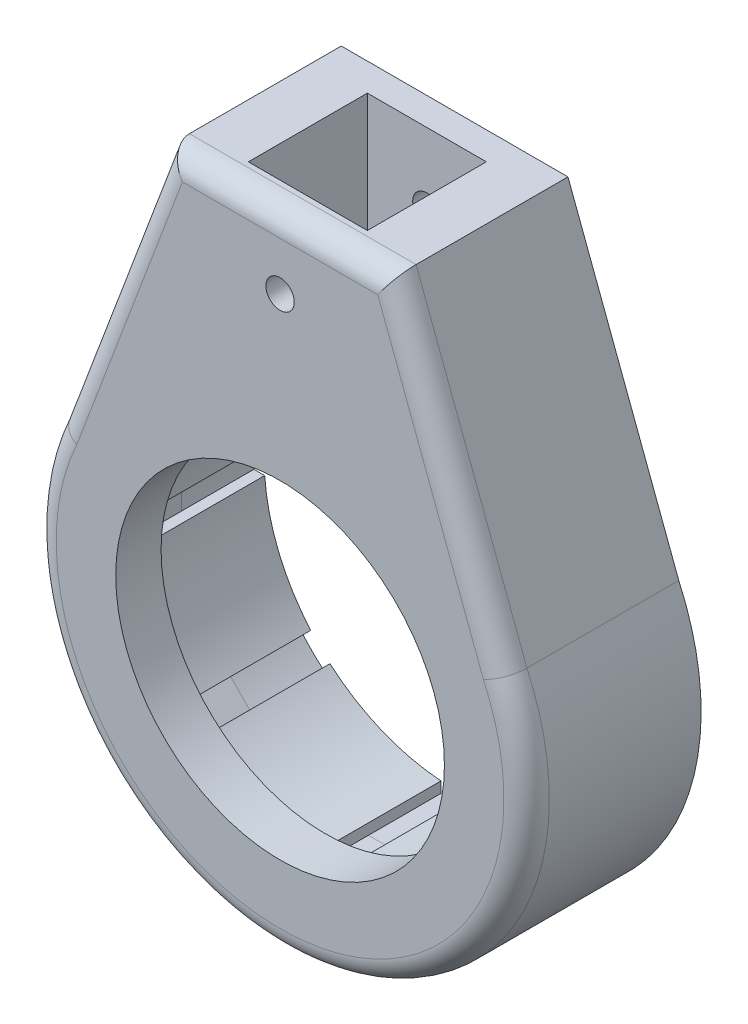
SolidWorks part; units mm, degrees
ref_plane "Alzado" through (0, 0, 0) normal (0, 0, 1) x (1, 0, 0)
ref_plane "Planta" through (0, 0, 0) normal (0, 1, 0) x (1, 0, 0)
ref_plane "Vista lateral" through (0, 0, 0) normal (1, 0, 0) x (0, 0, -1)
sketch "Croquis1" plane through (0, 0, 0) normal (0, 0, 1) x (1, 0, 0)
  line L0 (-43.5, 0) -> (43.5, 0) construction
  line L1 (0, 43.5) -> (0, -43.5) construction
  line L2 (0, 0) -> (-30.7591, 30.7591) construction
  line L3 (0, 0) -> (26.6453, -26.6453) construction
  line L4 (30.7591, 30.7591) -> (0, 0) construction
  line L5 (0, 0) -> (-30.7591, -30.7591) construction
  line L6 (-2.4, 33.5142) -> (-2.4, 35.4188)
  line L7 (2.4, 33.5142) -> (2.4, 35.4188)
  line L8 (2.4, -33.5142) -> (2.4, -35.4188)
  line L9 (-2.4, -33.5142) -> (-2.4, -35.4188)
  line L10 (-35.4188, 2.4) -> (-33.5142, 2.4)
  line L11 (-35.4188, -2.4) -> (-33.5142, -2.4)
  line L12 (35.4188, -2.4) -> (33.5142, -2.4)
  line L13 (35.4188, 2.4) -> (33.5142, 2.4)
  line L14 (-23.3478, 26.7419) -> (-22.001, 25.3952)
  line L15 (-26.7419, 23.3478) -> (-25.3952, 22.001)
  line L16 (26.7419, -23.3478) -> (25.3952, -22.001)
  line L17 (23.3478, -26.7419) -> (22.001, -25.3952)
  line L18 (22.001, 25.3952) -> (23.3478, 26.7419)
  line L19 (25.3952, 22.001) -> (26.7419, 23.3478)
  line L20 (-22.001, -25.3952) -> (-23.3478, -26.7419)
  line L21 (-25.3952, -22.001) -> (-26.7419, -23.3478)
  circle A0 centre (0, 0) radius 43.5
  arc A1 (-23.3478, 26.7419) -> (-26.7419, 23.3478) centre (0, 0) ccw
  arc A2 (-2.4, 33.5142) -> (-22.001, 25.3952) centre (0, 0) ccw
  arc A3 (2.4, 35.4188) -> (-2.4, 35.4188) centre (0, 0) ccw
  arc A4 (-25.3952, 22.001) -> (-33.5142, 2.4) centre (0, 0) ccw
  arc A5 (22.001, 25.3952) -> (2.4, 33.5142) centre (0, 0) ccw
  arc A6 (26.7419, 23.3478) -> (23.3478, 26.7419) centre (0, 0) ccw
  arc A7 (33.5142, 2.4) -> (25.3952, 22.001) centre (0, 0) ccw
  arc A8 (35.4188, -2.4) -> (35.4188, 2.4) centre (0, 0) ccw
  arc A9 (25.3952, -22.001) -> (33.5142, -2.4) centre (0, 0) ccw
  arc A10 (23.3478, -26.7419) -> (26.7419, -23.3478) centre (0, 0) ccw
  arc A11 (2.4, -33.5142) -> (22.001, -25.3952) centre (0, 0) ccw
  arc A12 (-2.4, -35.4188) -> (2.4, -35.4188) centre (0, 0) ccw
  arc A13 (-22.001, -25.3952) -> (-2.4, -33.5142) centre (0, 0) ccw
  arc A14 (-26.7419, -23.3478) -> (-23.3478, -26.7419) centre (0, 0) ccw
  arc A15 (-33.5142, -2.4) -> (-25.3952, -22.001) centre (0, 0) ccw
  arc A16 (-35.4188, 2.4) -> (-35.4188, -2.4) centre (0, 0) ccw
  dimension "D1" = 87
  dimension "D2" = 71
  dimension "D6" = 67.2
  dimension "D3" = 45
  dimension "D4" = 45
  dimension "D5" = 45
  dimension "D7" = 2.4
  dimension "D8" = 2.4
  dimension "D9" = 2.4
  dimension "D10" = 2.4
  dimension "D11" = 2.4
  dimension "D12" = 2.4
  dimension "D13" = 2.4
  dimension "D14" = 2.4
extrude "Saliente-Extruir4" add sketch "Croquis1" along normal blind 12.8 contours A0 | L14 A2 L6 A3 L7 A5 L18 A6 L19 A7 L13 A8 L12 A9 L16 A10 L17 A11 L8 A12 L9 A13 L20 A14 L21 A15 L11 A16 L10 A4 L15 A1
sketch "Croquis2" plane through (0, 0, 12.8) normal (0, 0, 1) x (1, 0, 0)
  line L0 (0, 0) -> (0, 115.8162) construction
  circle A0 centre (0, 0) radius 43.5
  dimension "D1" = 87
extrude "Saliente-Extruir5" add sketch "Croquis2" along normal blind 18
sketch "Croquis3" plane through (0, 0, 0) normal (0, 0, 1) x (1, 0, 0)
  line L0 (-43.5, 0) -> (43.5, 0) construction
  line L1 (43.5, 0) -> (20, 70) construction
  line L2 (20, 70) -> (-20, 70) construction
  line L3 (-20, 70) -> (-43.5, 0) construction
  line L4 (0, 0) -> (0, 70) construction
  line L5 (-20, 70) -> (-39.5567, 18.0975)
  line L6 (20, 70) -> (39.5567, 18.0975)
  line L7 (-20, 70) -> (20, 70)
  circle A0 centre (0, 0) radius 43.5 construction
  circle A2 centre (0, 0) radius 43.5
  arc A3 (39.5567, 18.0975) -> (-39.5567, 18.0975) centre (0, 0) ccw
  dimension "D1" = 70
  dimension "D2" = 40
  dimension "D3" = 20
  dimension "D4" = 51.9025
  dimension "D5" = 55.4647
  dimension "D6" = 0
extrude "Saliente-Extruir6" add sketch "Croquis3" along normal through all
sketch "Croquis4" plane through (0, 70, 0) normal (0, 1, 0) x (1, 0, 0)
  line L0 (0, 0) -> (0, -30.8) construction
  line L1 (20, -30.8) -> (-20, -30.8) construction
  line L2 (-20, -15.4) -> (20, -15.4) construction
  line L3 (-20, -30.8) -> (-20, 0) construction
  line L4 (20, -30.8) -> (20, 0) construction
  line L6 (-10.5, -4.9) -> (10.5, -4.9)
  line L7 (-10.5, -4.9) -> (-10.5, -25.9)
  line L8 (-10.5, -25.9) -> (10.5, -25.9)
  line L9 (10.5, -4.9) -> (10.5, -25.9)
  line L10 (-10.5, -4.9) -> (10.5, -25.9) construction
  line L11 (-10.5, -25.9) -> (10.5, -4.9) construction
  point P11 (0, -15.4)
  dimension "D1" = 21
  dimension "D2" = 21
extrude "Cortar-Extruir1" cut sketch "Croquis4" against normal blind 25
sketch "Croquis5" plane through (0, 0, 0) normal (0, 0, -1) x (-1, 0, 0)
  line L0 (0, 0) -> (0, 70) construction
  line L1 (-20, 70) -> (20, 70) construction
  circle A0 centre (0, 57.5) radius 2.5
  dimension "D1" = 5
  dimension "D2" = 12.5
extrude "Cortar-Extruir2" cut sketch "Croquis5" against normal blind 42
sketch "Croquis6" plane through (0, 0, 12.8) normal (0, 0, -1) x (-1, 0, 0)
  line L0 (-2.4, 33.5142) -> (-2.4, 35.4188)
  line L1 (-2.4, 35.4188) -> (2.4, 35.4188)
  line L2 (2.4, 35.4188) -> (2.4, 33.5142)
  line L3 (22.001, 25.3952) -> (23.3478, 26.7419)
  line L4 (23.3478, 26.7419) -> (26.7419, 23.3478)
  line L5 (26.7419, 23.3478) -> (25.3952, 22.001)
  line L6 (-22.001, 25.3952) -> (-23.3478, 26.7419)
  line L7 (-23.3478, 26.7419) -> (-26.7419, 23.3478)
  line L8 (-26.7419, 23.3478) -> (-25.3952, 22.001)
  line L9 (33.5142, 2.4) -> (35.4188, 2.4)
  line L10 (35.4188, 2.4) -> (35.4188, -2.4)
  line L11 (35.4188, -2.4) -> (33.5142, -2.4)
  line L12 (25.3952, -22.001) -> (26.7419, -23.3478)
  line L13 (26.7419, -23.3478) -> (23.3478, -26.7419)
  line L14 (23.3478, -26.7419) -> (22.001, -25.3952)
  line L15 (2.4, -33.5142) -> (2.4, -35.4188)
  line L16 (2.4, -35.4188) -> (-2.4, -35.4188)
  line L17 (-2.4, -33.5142) -> (-2.4, -35.4188) construction
  line L18 (-2.4, -33.5142) -> (-2.4, -35.4188) construction
  line L19 (-2.4, -35.4188) -> (-2.4, -33.5142)
  line L20 (-22.001, -25.3952) -> (-23.3478, -26.7419)
  line L21 (-23.3478, -26.7419) -> (-26.7419, -23.3478)
  line L22 (-26.7419, -23.3478) -> (-25.3952, -22.001)
  line L23 (-33.5142, -2.4) -> (-35.4188, -2.4)
  line L24 (-35.4188, -2.4) -> (-35.4188, 2.4)
  line L25 (-35.4188, 2.4) -> (-33.5142, 2.4)
  arc A0 (22.001, 25.3952) -> (2.4, 33.5142) centre (0, 0) ccw
  arc A1 (-2.4, 33.5142) -> (-22.001, 25.3952) centre (0, 0) ccw
  arc A2 (-25.3952, 22.001) -> (-33.5142, 2.4) centre (0, 0) ccw
  arc A3 (-33.5142, -2.4) -> (-25.3952, -22.001) centre (0, 0) ccw
  arc A4 (33.5142, 2.4) -> (25.3952, 22.001) centre (0, 0) ccw
  arc A5 (-22.001, -25.3952) -> (-2.4, -33.5142) centre (0, 0) ccw
  arc A6 (2.4, -33.5142) -> (22.001, -25.3952) centre (0, 0) ccw
  arc A7 (25.3952, -22.001) -> (33.5142, -2.4) centre (0, 0) ccw
extrude "Cortar-Extruir3" cut sketch "Croquis6" against normal blind 10
sketch "Croquis7" plane through (0, 0, 22.8) normal (0, 0, -1) x (-1, 0, 0)
  circle A0 centre (0, 0) radius 29
  dimension "D1" = 58
extrude "Cortar-Extruir4" cut sketch "Croquis7" against normal blind 10
fillet "Redondeo1" radius 4 4 edges at (0, 70, 30.8) (0, -43.5, 30.8) (29.7783, 44.0487, 30.8) (-29.7783, 44.0487, 30.8)
